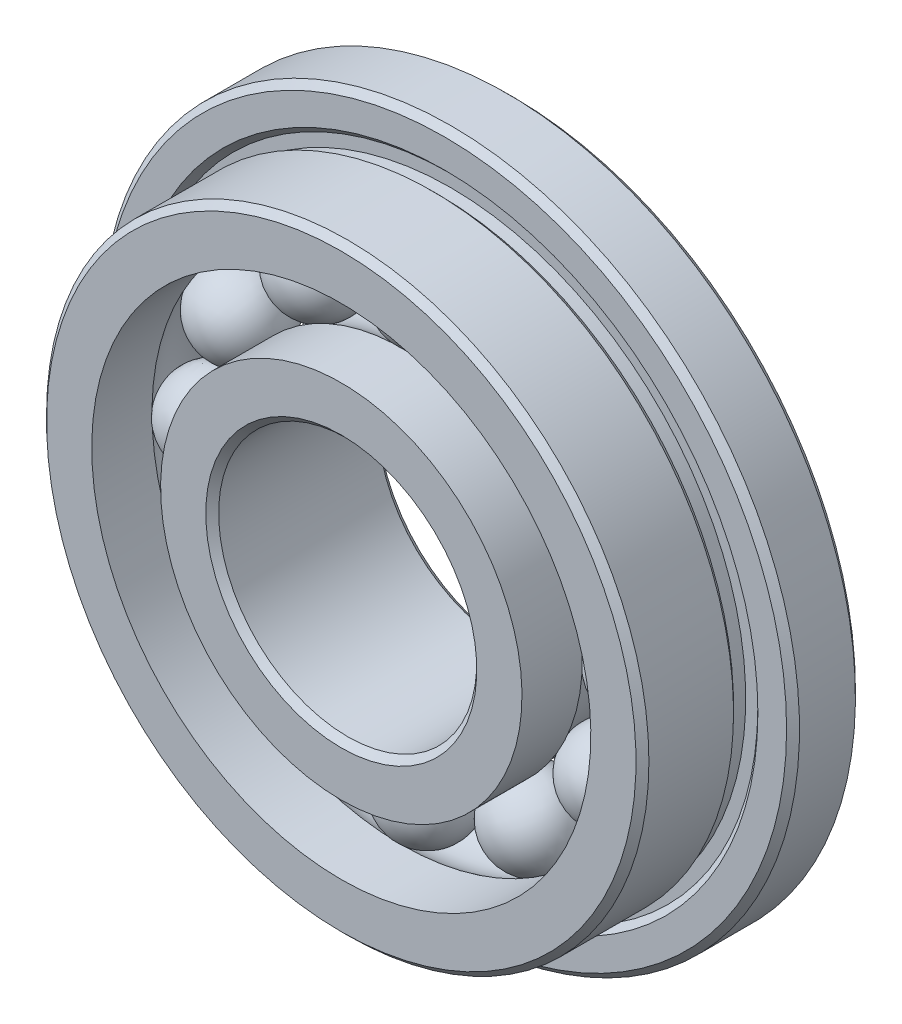
SolidWorks part; units mm, degrees
ref_plane "Front Plane" through (0, 0, 0) normal (0, 0, 1) x (1, 0, 0)
ref_plane "Top Plane" through (0, 0, 0) normal (0, 1, 0) x (1, 0, 0)
ref_plane "Right Plane" through (0, 0, 0) normal (1, 0, 0) x (0, 0, -1)
sketch "Sketch1" plane through (0, 0, 0) normal (1, 0, 0) x (0, 0, -1)
  line L0 (0, 3.5) -> (0, -3.5) construction
  line L1 (-1, 3.5) -> (1, 3.5) construction
  line L2 (0, 0) -> (1, 0) construction
  line L3 (1, 4.05) -> (1, -4.05) construction
  line L4 (1, -4.05) -> (0.2, -4.05) construction
  line L5 (1, 1.5) -> (0, 1.5) construction
  line L6 (1, 1.5) -> (1, -1.5) construction
  dimension "OD" = 7
  dimension "Width" = 2
  dimension "Flange Dia." = 8.1
  dimension "Flange Thickness" = 0.8
  dimension "ID" = 3
sketch "Sketch2" plane through (0, 0, 0) normal (1, 0, 0) x (0, 0, -1)
  line L0 (1, 4.05) -> (0.2, 4.05)
  line L1 (0.2, 4.05) -> (0.2, 3.6414)
  line L2 (0.0586, 3.5) -> (-1, 3.5)
  line L3 (-1, 3.5) -> (-1, 2.9)
  line L4 (-1, 2.9) -> (-0.3, 2.9)
  line L5 (1, 4.05) -> (1, -4.05) construction
  line L6 (1, 2.9) -> (1, 4.05)
  line L7 (1, 1.5) -> (-1, 1.5)
  line L8 (-1, 1.5) -> (-1, 2.1)
  line L9 (-1, 2.1) -> (-0.3, 2.1)
  line L10 (1, 2.1) -> (1, 1.5)
  line L11 (0, 3.5) -> (0, 1.5) construction
  line L12 (-0.5, 2.5) -> (0.5, 2.5) construction
  line L13 (0.3, 2.9) -> (1, 2.9)
  line L14 (0.3, 2.1) -> (1, 2.1)
  line L15 (0.2, 3.6414) -> (0.2707, 3.5707)
  line L16 (0.2707, 3.5707) -> (0.2707, 3.4293)
  line L17 (0.2707, 3.4293) -> (0.1293, 3.4293)
  line L18 (0.1293, 3.4293) -> (0.0586, 3.5)
  line L19 (0.2, 3.5) -> (0.2707, 3.4293) construction
  line L20 (0.2707, 3.5707) -> (0.1293, 3.4293) construction
  line L21 (0.0586, 3.5) -> (0.2, 3.5) construction
  line L22 (0.2, 3.5) -> (0.2, 3.6414) construction
  circle A0 centre (0, 2.5) radius 0.5 construction
  arc A1 (-0.3, 2.9) -> (0.3, 2.9) centre (0, 2.5) cw
  arc A2 (-0.3, 2.1) -> (0.3, 2.1) centre (0, 2.5) ccw
  dimension "Ball Dia." = 1
  dimension "D2" = 135
  dimension "D3" = 0.2
  dimension "D4" = 0.8
  dimension "Race Thikness" = 0.6
revolve "Revolve1" add sketch "Sketch2" angle 360 about L2
fillet "Fillet1" radius 0.075 3 edges at (0, -4.05, -1) (0, -4.05, -0.2) (0, -3.5, 1) profile chamfer
sketch "Sketch3" plane through (0, 0, 0) normal (0, 0, 1) x (1, 0, 0)
  line L0 (-1.5, 0) -> (1.5, 0) construction
  line L1 (-3.5, 0) -> (3.5, 0) construction
  point P5 (0, 0)
  dimension "ID2" = 3
  dimension "OD2" = 7
fillet "Fillet2" radius 0.075 2 edges at (0, -1.5, -1) (0, -1.5, 1) profile chamfer
sketch "Sketch7" plane through (0, 0, 0) normal (0, 0, 1) x (1, 0, 0)
  line L0 (0, 3) -> (0, 2)
  line L1 (0, 4.05) -> (0, -4.05) construction
  line L2 (-0.6124, 3) -> (0, 0) construction
  line L3 (0, 0) -> (0.6124, 3) construction
  line L4 (0.6124, 3) -> (-0.6124, 3) construction
  circle A0 centre (0, 2.5) radius 0.5 construction
  circle A1 centre (0, 0) radius 3 construction
  circle A2 centre (0, 0) radius 2 construction
  arc A4 (0, 3) -> (0, 2) centre (0, 2.5) ccw
  dimension "D1" = 23.074
revolve "Revolve3" add sketch "Sketch7" angle 360 about L0
pattern_circular "CirPattern3" count 12 over 360 about axis through (0, 0, 0) along (0, 0, -1) of bodies 107
sketch "Sketch8" plane through (0, 0, 0) normal (1, 0, 0) x (0, 0, -1)
  line L0 (-1, 3.5) -> (1, 3.5) construction
  line L1 (1, 3.5) -> (1, 4.05) construction
  line L2 (-1, -3.5) -> (1, -3.5) construction
  line L3 (1, 4.05) -> (1, -4.05) construction
  dimension "D1" = 7
equation "\"Ball Dia.@Sketch2\"=\"D1@Sketch2\"*.5"
equation "\"D3@Sketch2\"=\"Flange Thickness@Sketch1\"/4"
equation "\"D1@Fillet1\" = \"Race Thickness@Sketch2\" / 8"
equation "\"ID2@Sketch3\" = \"ID@Sketch1\""
equation "\"OD2@Sketch3\" = \"OD@Sketch1\""
equation "\"D1@Fillet2\" = \"Race Thickness@Sketch2\" / 8"
equation "\"D1@CirPattern3\"=360/\"D1@Sketch7\"-4"
equation "\"D4@Sketch2\"=\"D1@Sketch2\"*.4"
